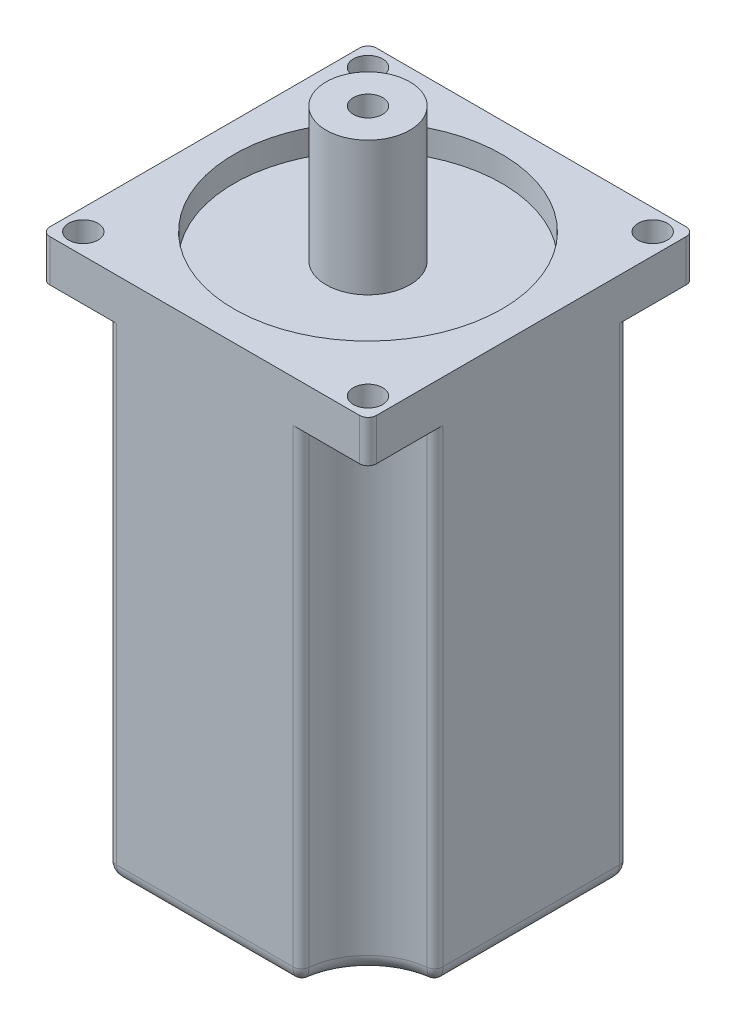
SolidWorks part; units mm, degrees
ref_plane "Front Plane" through (0, 0, 0) normal (0, 0, 1) x (1, 0, 0)
ref_plane "Top Plane" through (0, 0, 0) normal (0, 1, 0) x (1, 0, 0)
ref_plane "Right Plane" through (0, 0, 0) normal (1, 0, 0) x (0, 0, -1)
sketch "Sketch1" plane through (0, 0, 0) normal (0, 1, 0) x (1, 0, 0)
  line L1 (-19.5, 19.5) -> (19.5, 19.5)
  line L2 (-19.5, 19.5) -> (-19.5, -19.5)
  line L3 (-19.5, -19.5) -> (19.5, -19.5)
  line L4 (19.5, 19.5) -> (19.5, -19.5)
  line L5 (-19.5, 19.5) -> (19.5, -19.5) construction
  line L6 (-19.5, -19.5) -> (19.5, 19.5) construction
  point P0 (0, 0)
  dimension "D1" = 39
  dimension "D2" = 39
extrude "Boss-Extrude1" add sketch "Sketch1" along normal blind 58
sketch "Sketch2" plane through (0, 0, 0) normal (0, 0, 1) x (1, 0, 0)
  line L0 (0, 58) -> (0, 72.5) construction
  line L1 (-19.5, 58) -> (19.5, 58) construction
  line L2 (0, 58) -> (0, 72.5) construction
  line L3 (1.75, 76) -> (5, 76)
  line L4 (5, 76) -> (5, 60)
  line L5 (5, 60) -> (16, 60)
  line L6 (16, 60) -> (16, 63)
  line L7 (16, 63) -> (19.5, 63)
  line L8 (19.5, 63) -> (19.5, 58)
  line L9 (19.5, 58) -> (0, 58)
  line L10 (0, 58) -> (0, 72.5)
  line L11 (1.75, 76) -> (1.75, 72.5)
  line L12 (1.75, 72.5) -> (0, 72.5)
  dimension "D1" = 18
  dimension "D2" = 10
  dimension "D3" = 2
  dimension "D4" = 3
  dimension "D5" = 3.5
  dimension "D6" = 1.75
  dimension "D7" = 3.5
revolve "Revolve1" add sketch "Sketch2" angle 360 about L10
sketch "Sketch3" plane through (0, 58, 0) normal (0, 1, 0) x (1, 0, 0)
  line L2 (19.5, -19.5) -> (19.5, 0)
  line L3 (0, -19.5) -> (19.5, -19.5)
  line L4 (19.5, -19.5) -> (19.5, 0)
  line L5 (0, -19.5) -> (19.5, -19.5)
  line L6 (-19.5, -19.5) -> (0, -19.5)
  line L7 (-19.5, 0) -> (-19.5, -19.5)
  line L8 (-19.5, -19.5) -> (0, -19.5)
  line L9 (-19.5, 0) -> (-19.5, -19.5)
  line L10 (-19.5, 19.5) -> (-19.5, 0)
  line L11 (0, 19.5) -> (-19.5, 19.5)
  line L12 (-19.5, 19.5) -> (-19.5, 0)
  line L13 (0, 19.5) -> (-19.5, 19.5)
  line L14 (19.5, 19.5) -> (0, 19.5)
  line L15 (19.5, 0) -> (19.5, 19.5)
  line L16 (19.5, 19.5) -> (0, 19.5)
  line L17 (19.5, 0) -> (19.5, 19.5)
  circle A0 centre (0, 0) radius 19.5 construction
  arc A1 (0, -19.5) -> (19.5, 0) centre (0, 0) ccw
  arc A3 (-19.5, 0) -> (0, -19.5) centre (0, 0) ccw
  arc A5 (0, 19.5) -> (-19.5, 0) centre (0, 0) ccw
  arc A7 (19.5, 0) -> (0, 19.5) centre (0, 0) ccw
  arc A8 (0, 19.5) -> (-19.5, 0) centre (0, 0) ccw construction
  circle A9 centre (0, 0) radius 19.5
  arc A10 (0, 19.5) -> (-19.5, 0) centre (0, 0) ccw
  line M13 (19.5, -19.5) -> (19.5, 0)
  arc M14 (19.5, 0) -> (0, -19.5) centre (0, 0) cw
  line M15 (0, -19.5) -> (19.5, -19.5)
  dimension "D1" = 0
  dimension "D2" = 0
  dimension "D3" = 0
  dimension "D4" = 0
extrude "Boss-Extrude2" add sketch "Sketch3" along direction (0, 1, 0) on the side of the normal blind 5 contours M15 M13 M14 | A9 L17 L16 | A9 L9 L8 | A9 L13 L12 region at (15.1443, 58, 15.1443) region at (15.1443, 58, -15.1443) region at (-15.1443, 58, 15.1443) region at (-15.1443, 58, -15.1443)
sketch "Sketch4" plane through (0, 0, 0) normal (0, -1, 0) x (1, 0, 0)
  circle A0 centre (-19.5, -19.5) radius 8
  circle A1 centre (19.5, -19.5) radius 8
  circle A2 centre (19.5, 19.5) radius 8
  circle A3 centre (-19.5, 19.5) radius 8
  dimension "D1" = 16
extrude "Cut-Extrude1" cut sketch "Sketch4" against normal blind 58
fillet "Fillet1" radius 2 8 edges at (19.5, 0, 0) (0, 0, -19.5) (-19.5, 0, 0) (0, 0, 19.5) (-13.8431, 0, 13.8431) (-13.8431, 0, -13.8431) (13.8431, 0, -13.8431) (13.8431, 0, 13.8431) type face fillet first side face at (0, 0, 0) second side face at (14.6716, 29, -14.6716) second side face at (19.5, 44.75, 0) second side face at (14.6716, 29, 14.6716) second side face at (0, 44.75, 19.5) second side face at (-14.6716, 29, 14.6716) second side face at (-19.5, 44.75, 0) second side face at (-14.6716, 29, -14.6716) second side face at (0, 44.75, -19.5)
fillet "Fillet2" radius 1 16 edges at (-19.2371, 1.0088, 11.2413) (-19.2371, 1.0088, -11.2413) (-11.2413, 1.0088, -19.2371) (11.2413, 1.0088, -19.2371) (19.2371, 1.0088, -11.2413) (-11.2413, 1.0088, 19.2371) (19.2371, 1.0088, 11.2413) (11.2413, 1.0088, 19.2371) (-19.5, 30, 11.5) (-19.5, 30, -11.5) (-11.5, 30, -19.5) (11.5, 30, -19.5) (19.5, 30, -11.5) (-11.5, 30, 19.5) (19.5, 30, 11.5) (11.5, 30, 19.5)
fillet "Fillet3" radius 1 4 edges at (-19.5, 60.5, 19.5) (-19.5, 60.5, -19.5) (19.5, 60.5, -19.5) (19.5, 60.5, 19.5)
sketch "Sketch5" plane through (0, 0, 0) normal (1, 0, 0) x (0, 0, -1)
  line L0 (0, 0) -> (0, 105.6657) construction
  line L1 (-18.5, 63) -> (18.5, 63) construction
  line L2 (0, 2.8) -> (16.5, 2.8)
  line L3 (0, 2.8) -> (0, 56.5)
  line L4 (0, 56.5) -> (16.5, 56.5)
  line L5 (16.5, 2.8) -> (16.5, 56.5)
  line L6 (19.5, 58) -> (19.5, 2) construction
  line L7 (9.702, 0) -> (17.5, 0) construction
  dimension "D1" = 6.5
  dimension "D2" = 3
  dimension "D3" = 2.8
revolve "Cut-Revolve1" cut sketch "Sketch5" angle 360 about L0
sketch "Sketch6" plane through (0, 58, 0) normal (0, -1, 0) x (1, 0, 0)
  line L1 (-17, -17) -> (17, -17) construction
  line L2 (-17, -17) -> (-17, 17) construction
  line L3 (-17, 17) -> (17, 17) construction
  line L4 (17, -17) -> (17, 17) construction
  line L5 (-17, -17) -> (17, 17) construction
  line L6 (-17, 17) -> (17, -17) construction
  circle A0 centre (17, 17) radius 1.75
  circle A1 centre (17, -17) radius 1.75
  circle A2 centre (-17, -17) radius 1.75
  circle A3 centre (-17, 17) radius 1.75
  point P0 (0, 0)
  point P20 (0, 0)
  dimension "D1" = 3.5
  dimension "D2" = 34
  dimension "D3" = 34
  dimension "D4" = 4
extrude "Cut-Extrude2" cut sketch "Sketch6" against normal through all
